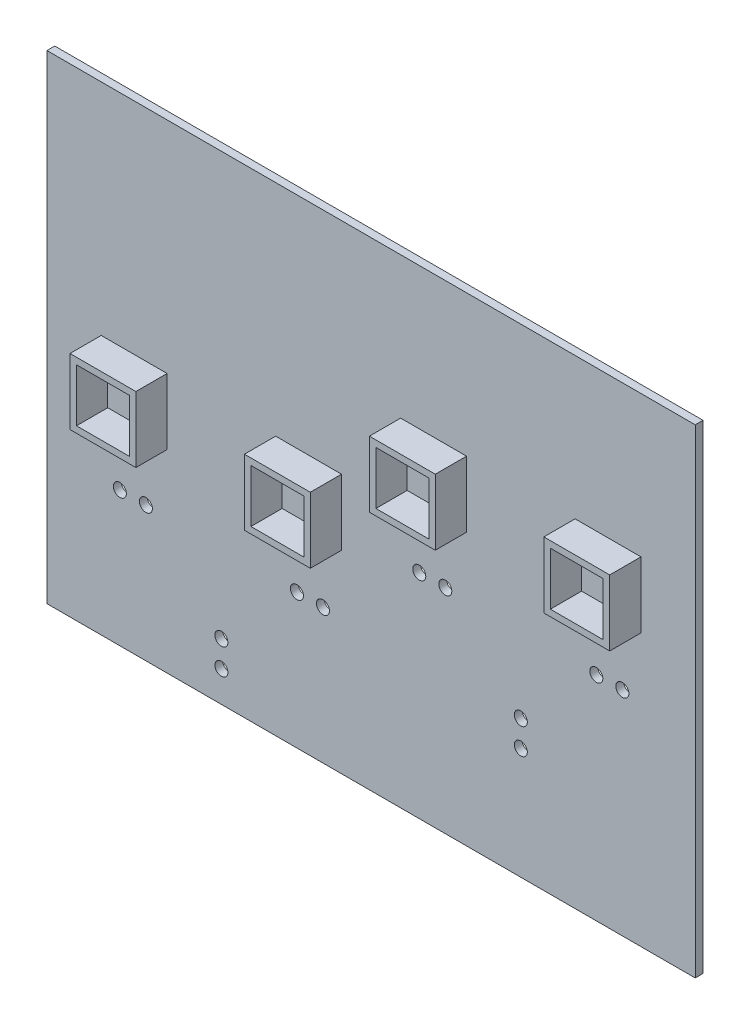
SolidWorks part; units mm, degrees
material "6061-T6 (SS)"
ref_plane "Front" through (0, 0, 0) normal (0, 0, 1) x (1, 0, 0)
ref_plane "Top" through (0, 0, 0) normal (0, 1, 0) x (1, 0, 0)
ref_plane "Right" through (0, 0, 0) normal (1, 0, 0) x (0, 0, -1)
sketch "Croquis1" plane through (0, 0, 0) normal (0, 0, 1) x (1, 0, 0)
  line L1 (-67, -27) -> (67, -27)
  line L2 (-67, -27) -> (-67, 27)
  line L3 (-67, 27) -> (67, 27)
  line L4 (67, -27) -> (67, 27)
  line L5 (-67, -27) -> (67, 27) construction
  line L6 (-67, 27) -> (67, -27) construction
  circle A0 centre (0, 0) radius 5 construction
  point P0 (0, 0)
  dimension "D3" = 10
  dimension "D1" = 54
  dimension "D2" = 134
extrude "Saliente-Extruir1" add sketch "Croquis1" along normal blind 3
sketch "Croquis2" plane through (0, 0, 3) normal (0, 0, 1) x (1, 0, 0)
  line L7 (-43.65, -10.15) -> (-23.35, -10.15)
  line L19 (-43.65, 10.15) -> (-23.35, 10.15)
  line L44 (0, 0) -> (0, 33.654) construction
  line L86 (-43.65, -10.15) -> (-23.35, 10.15) construction
  line L87 (-43.65, 10.15) -> (-23.35, -10.15) construction
  line L93 (-33.5, 0) -> (0, 0) construction
  line L94 (-43.65, -10.15) -> (-43.65, 10.15)
  line L95 (-23.35, -10.15) -> (-23.35, 10.15)
  line L96 (-46.15, -12.65) -> (-20.85, -12.65)
  line L101 (-20.85, -12.65) -> (-20.85, 12.65)
  line L102 (-46.15, 12.65) -> (-20.85, 12.65)
  line L105 (-67, 27) -> (-67, -27) construction
  line L106 (67, 27) -> (-67, 27) construction
  line L109 (-46.15, -12.65) -> (-46.15, 12.65)
  line L134 (-46.15, 0) -> (-41.15, 0) construction
  line L135 (-41.15, 0) -> (-41.15, 0) construction
  line L136 (-41.15, 0) -> (-46.15, 0) construction
  line L137 (-46.15, 0) -> (-46.15, 12.65) construction
  line L138 (-46.15, -12.65) -> (-46.15, 0) construction
  line L139 (-20.85, -12.65) -> (-20.85, 0) construction
  line L140 (-25.85, 0) -> (-20.85, 0) construction
  line L141 (-25.85, 0) -> (-25.85, 0) construction
  line L142 (-20.85, 0) -> (-25.85, 0) construction
  line L143 (-20.85, 0) -> (-20.85, 12.65) construction
  line L160 (-43.65, 2.5) -> (-38.65, 2.5) construction
  line L161 (-43.65, 2.5) -> (-43.65, 10.15) construction
  line L163 (-38.65, -2.5) -> (-43.65, -2.5) construction
  line L164 (-43.65, -10.15) -> (-43.65, -2.5) construction
  line L166 (-38.65, 2.5) -> (-38.65, -2.5) construction
  line L169 (-23.35, 2.5) -> (-28.35, 2.5) construction
  line L170 (-28.35, 2.5) -> (-28.35, -2.5) construction
  line L172 (-28.35, -2.5) -> (-23.35, -2.5) construction
  line L174 (-23.35, 2.5) -> (-23.35, 10.15) construction
  line L176 (-23.35, -10.15) -> (-23.35, -2.5) construction
  line L203 (46.15, -12.65) -> (20.85, -12.65)
  line L204 (46.15, -12.65) -> (46.15, 12.65)
  line L205 (46.15, 12.65) -> (20.85, 12.65)
  line L206 (20.85, -12.65) -> (20.85, 12.65)
  line L207 (43.65, -10.15) -> (23.35, -10.15)
  line L208 (23.35, -10.15) -> (23.35, 10.15)
  line L209 (43.65, 10.15) -> (23.35, 10.15)
  line L210 (43.65, -10.15) -> (43.65, 10.15)
  point P0 (-33.5, 0)
  dimension "D1" = 33.5
  dimension "D2" = 20.3
  dimension "D3" = 20.3
  dimension "D6" = 2.5
extrude "Saliente-Extruir2" add sketch "Croquis2" along normal blind 12
move or copy body "Sólido-Mover/Copiar1" bodies to move or copy 102 copy yes number of copies 1 translate (115, 30, 0)
combine bodies "Combinar1" operation type add bodies to combine 104 102
sketch "Croquis4" plane through (0, 0, 3) normal (0, 0, 1) x (1, 0, 0)
  line L0 (-33.5, 0) -> (33.5, 0) construction
  line L1 (71.35, 30) -> (91.65, 30) construction
  line L2 (71.35, 40.15) -> (71.35, 19.85) construction
  line L4 (91.65, 19.85) -> (91.65, 40.15) construction
  circle A0 centre (-33.5, 0) radius 2
  circle A1 centre (33.5, 0) radius 2
  circle A2 centre (0, 0) radius 5 construction
  circle A3 centre (81.5, 30) radius 2
  circle A4 centre (148.5, 30) radius 2
  dimension "D1" = 4
  dimension "D2" = 33.5
  dimension "D3" = 33.5
  dimension "D4" = 4
  dimension "D6" = 67
extrude "Cortar-Extruir1" cut sketch "Croquis4" against normal blind 12
sketch "Croquis5" plane through (0, 0, 3) normal (0, 0, 1) x (1, 0, 0)
  line L1 (48, 57) -> (-67, 57)
  line L2 (48, 57) -> (48, 27)
  line L3 (48, 27) -> (-67, 27)
  line L4 (-67, 57) -> (-67, 27)
  line L5 (67, -27) -> (182, -27)
  line L6 (67, -27) -> (67, 3)
  line L7 (67, 3) -> (182, 3)
  line L8 (182, -27) -> (182, 3)
extrude "Saliente-Extruir3" add sketch "Croquis5" against normal up to surface (3 mm away) up to face at (-35.5, 0, 0)
sketch "Croquis6" plane through (0, 0, 3) normal (0, 0, 1) x (1, 0, 0)
  line L0 (182, -27) -> (182, 57) construction
  line L5 (182, -27) -> (182, 57) construction
  line L6 (-67, 57) -> (182, 57)
  line L7 (-67, -27) -> (182, -27)
  line L8 (-67, -27) -> (-67, -87)
  line L9 (-67, -87) -> (182, -87)
  line L10 (182, -27) -> (182, -87)
  line L11 (-67, 57) -> (-67, 97)
  line L12 (-67, 97) -> (182, 97)
  line L13 (182, 57) -> (182, 97)
  dimension "D1" = 60
  dimension "D2" = 40
extrude "Saliente-Extruir4" add sketch "Croquis6" against normal up to surface (3 mm away) up to face at (57.5, 15, 0)
sketch "Croquis8" plane through (0, 0, 3) normal (0, 0, 1) x (1, 0, 0)
  line L0 (68.85, 2.35) -> (161.15, 2.35) construction
  line L1 (115, 2.35) -> (115, 40.5405) construction
  line L2 (68.85, 42.65) -> (68.85, 17.35) construction
  line L3 (161.15, 17.35) -> (161.15, 42.65) construction
  line L4 (135.85, 17.35) -> (161.15, 17.35) construction
  line L5 (160, 2.35) -> (160, -7.5082) construction
  line L6 (182, -87) -> (182, 97) construction
  line L7 (135, 2.35) -> (135, -4.8412) construction
  line L8 (122.5, 2.35) -> (122.5, -50.15) construction
  line L9 (-67, -87) -> (182, -87) construction
  line L10 (122.5, -25.15) -> (98.4739, -25.15) construction
  line L11 (-67, 97) -> (-67, -87) construction
  line L12 (-46.15, -12.65) -> (-20.85, -12.65) construction
  line L13 (0, 0) -> (0, -75.15) construction
  line L15 (20.85, -12.65) -> (46.15, -12.65) construction
  circle A0 centre (144, -5.15) radius 2.5
  circle A1 centre (154, -5.15) radius 2.5
  circle A2 centre (115, -34.15) radius 2.5
  circle A3 centre (115, -44.15) radius 2.5
  circle A4 centre (76, -5.15) radius 2.5
  circle A5 centre (86, -5.15) radius 2.5
  circle A6 centre (-29, -35.15) radius 2.5
  circle A7 centre (-39, -35.15) radius 2.5
  circle A8 centre (0, -65.15) radius 2.5
  circle A9 centre (0, -75.15) radius 2.5
  circle A10 centre (39, -35.15) radius 2.5
  circle A11 centre (29, -35.15) radius 2.5
  dimension "D1" = 15
  dimension "5" = 5
  dimension "D5" = 25
  dimension "D6" = 9
  dimension "D7" = 10
  dimension "D8" = 36.85
  dimension "D10" = 9
  dimension "D11" = 28
  dimension "D12" = 10
  dimension "D13" = 22.5
  dimension "D14" = 10
  dimension "D15" = 52.5
  dimension "D2" = 7.5
  dimension "D3" = 10
  dimension "D4" = 22
  dimension ".75" = 7.5
  dimension "D9" = 25
extrude "Cortar-Extruir3" cut sketch "Croquis8" against normal blind 10
